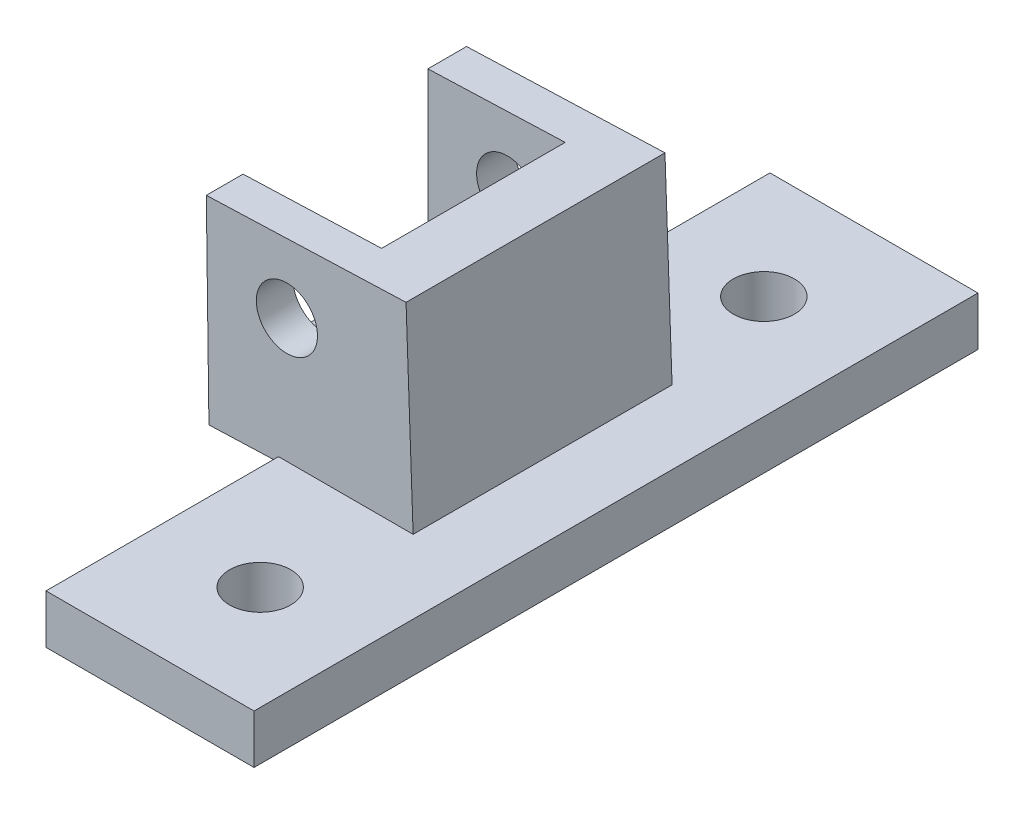
SolidWorks part; units mm, degrees
ref_plane "Front Plane" through (0, 0, 0) normal (0, 0, 1) x (1, 0, 0)
ref_plane "Top Plane" through (0, 0, 0) normal (0, 1, 0) x (1, 0, 0)
ref_plane "Right Plane" through (0, 0, 0) normal (1, 0, 0) x (0, 0, -1)
sketch "Sketch1" plane through (0, 0, 0) normal (0, 0, 1) x (1, 0, 0)
  line L0 (337.3168, 116.8505) -> (338.0523, 96.3659)
  line L1 (330.9022, 116.6201) -> (352.1622, 117.3835) construction
  line L2 (338.0523, 96.3659) -> (359.2436, 97.1267)
  line L3 (359.2436, 97.1267) -> (358.5081, 117.6113)
  line L4 (358.5081, 117.6113) -> (337.3168, 116.8505)
  line L5 (330.7578, 99.9164) -> (346.4865, 100.4811) construction
  line L6 (330.7578, 99.9164) -> (346.4865, 100.4811)
  line L7 (337.9156, 100.1734) -> (346.4865, 100.4811)
  arc A0 (346.4865, 100.4811) -> (352.6762, 103.0671) centre (346.1447, 110) ccw construction
  arc A1 (352.6762, 103.0671) -> (352.1622, 117.3835) centre (346.1447, 110) ccw construction
  arc A2 (346.4865, 100.4811) -> (352.6762, 103.0671) centre (346.1447, 110) ccw
  arc A3 (352.6762, 103.0671) -> (352.1622, 117.3835) centre (346.1447, 110) ccw
  arc A4 (352.1622, 117.3835) -> (352.6762, 103.0671) centre (346.1447, 110) cw
  arc A5 (352.6762, 103.0671) -> (346.4865, 100.4811) centre (346.1447, 110) cw
  dimension "D1" = 6.35
  dimension "D2" = 3.81
extrude "Boss-Extrude2" add sketch "Sketch1" against normal blind 23.0618 contours A3 A2 L6 L0 L2 L3 L4 region at (342.2118, 100.0264, 0)
sketch "Sketch5" plane through (0, 0, -23.0618) normal (0, 0, -1) x (-1, 0, 0)
  line L0 (-352.1622, 117.3835) -> (-337.9156, 116.872)
  line L1 (-337.9156, 116.872) -> (-337.9156, 100.1734)
  line L2 (-337.9156, 100.1734) -> (-346.4865, 100.4811)
  arc A0 (-346.4865, 100.4811) -> (-352.1622, 117.3835) centre (-346.1447, 110) cw
  circle A1 centre (-346.1447, 110) radius 3.175 construction
  circle A2 centre (-346.1447, 110) radius 3.175
  circle A3 centre (-346.1447, 110) radius 3.175
  arc M5 (-346.4865, 100.4811) -> (-352.1622, 117.3835) centre (-346.1447, 110) cw
  line M10 (-337.9156, 100.1734) -> (-346.4865, 100.4811)
extrude "Boss-Extrude3" add sketch "Sketch5" against normal up to surface (4.0118 mm away) contours L1 L0 A2 M5 M10 region at (345.0477, 116.8806, -23.0618)
sketch "Sketch6" plane through (0, 0, 0) normal (0, 0, 1) x (1, 0, 0)
  line L0 (337.7808, 116.8671) -> (338.0523, 96.3659)
  line L1 (330.9022, 116.6201) -> (352.1622, 117.3835) construction
  line L2 (338.0523, 96.3659) -> (359.2436, 97.1267)
  line L3 (359.2436, 97.1267) -> (358.5081, 117.6113)
  line L4 (358.5081, 117.6113) -> (352.1622, 117.3835) construction
  line L5 (359.2436, 97.1267) -> (358.5081, 117.6113) construction
  line L6 (358.5081, 117.6113) -> (337.7808, 116.8671)
  circle A0 centre (346.1447, 110) radius 3.175
extrude "Boss-Extrude5" add sketch "Sketch6" along normal blind 3.81
ref_plane "Plane1" through (0, 97.1267, 0) normal (0, 1, 0) x (1, 0, 0)
sketch "Sketch7" plane through (0, 97.1267, 0) normal (0, 1, 0) x (1, 0, 0)
  line L0 (359.2436, 23.0618) -> (359.2436, -3.81) construction
  line L1 (345.2736, 47.1918) -> (366.8636, 47.1918)
  line L2 (345.2736, 47.1918) -> (345.2736, -27.94)
  line L3 (345.2736, -27.94) -> (366.8636, -27.94)
  line L4 (366.8636, 47.1918) -> (366.8636, -27.94)
  circle A0 centre (356.0686, 35.7618) radius 3.175
  circle A1 centre (356.0686, -16.51) radius 3.175
  dimension "D5" = 11.43
  dimension "D8" = 6.35
  dimension "D9" = 6.35
  dimension "D1" = 24.13
  dimension "D2" = 24.13
  dimension "D3" = 7.62
  dimension "D4" = 21.59
  dimension "D6" = 11.43
  dimension "D7" = 10.795
  dimension "D10" = 10.795
extrude "Boss-Extrude6" add sketch "Sketch7" against normal blind 5.08 contours A0 | L2 L1 L4 L3
sketch "Sketch9" plane through (0, 97.1267, 0) normal (0, 1, 0) x (1, 0, 0)
  line L0 (345.2736, -3.81) -> (345.2736, -27.94) construction
  line L1 (345.2736, -27.94) -> (366.8636, -27.94) construction
  circle A0 centre (356.0686, -16.51) radius 3.175
  dimension "D1" = 10.795
  dimension "D3" = 6.35
  dimension "D2" = 11.43
extrude "Cut-Extrude1" cut sketch "Sketch9" against normal blind 228.6
